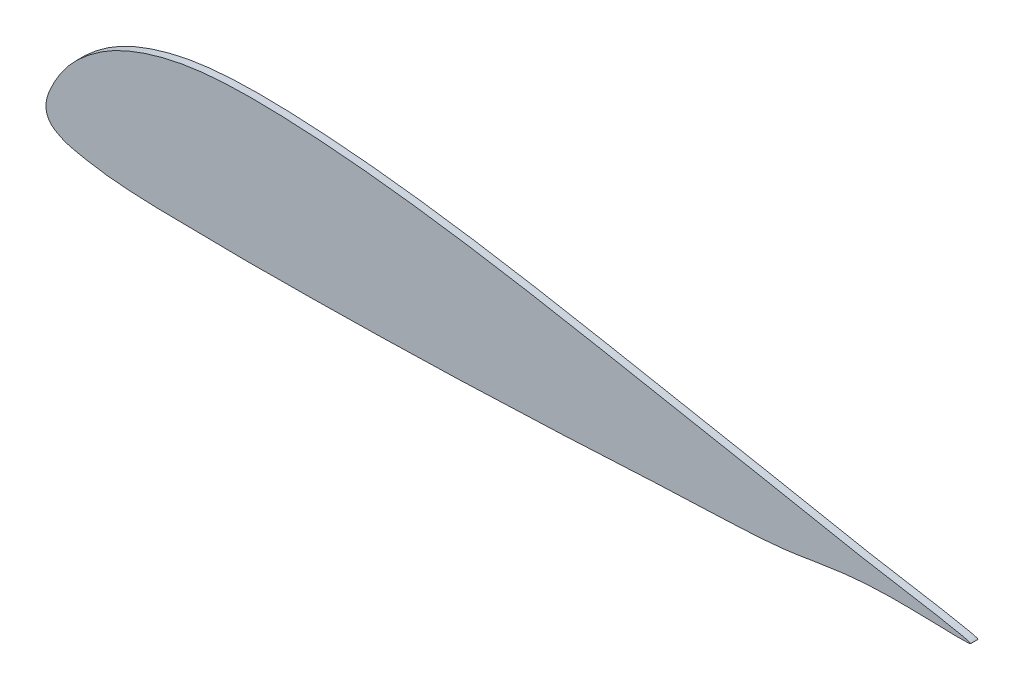
SolidWorks part; units mm, degrees
material "Cedar"
ref_plane "Front Plane" through (0, 0, 0) normal (0, 0, 1) x (1, 0, 0)
ref_plane "Top Plane" through (0, 0, 0) normal (0, 1, 0) x (1, 0, 0)
ref_plane "Right Plane" through (0, 0, 0) normal (1, 0, 0) x (0, 0, -1)
sketch "Sketch11" plane through (0, 0, 0) normal (0, 0, 1) x (1, 0, 0)
  line L0 (-43.8005, 0) -> (380.3083, 0) construction
  line L1 (0, 103.9604) -> (0, -61.3214) construction
  line L2 (71, 38.6091) -> (104.7082, 38.6091) construction
  line L3 (300.2276, 54.6091) -> (24.1354, 54.6091) construction
  line L4 (360.1442, 7.9921) -> (360.1442, 43.239) construction
  line L5 (104.7082, 38.6091) -> (88.9969, 38.6091) construction
  line L6 (250, 2.9185) -> (250, 63.6488) construction
  line L7 (150, 0.322) -> (150, 76.2348) construction
  line L8 (257, 52.6091) -> (310.8064, 52.6091)
  line L9 (26.8374, 56.6091) -> (71.2374, 56.6091)
  line L10 (53, 0.8986) -> (53, 69.6242)
  line L11 (57, 70.9042) -> (57, 0.7526)
  line L12 (71.2374, 56.6091) -> (142.6837, 56.6091)
  line L13 (147.6837, 61.6091) -> (147.6837, 76.3956)
  line L14 (151.6838, 76.1131) -> (151.6838, 61.6091)
  line L15 (156.6838, 56.6091) -> (243, 56.6091)
  line L16 (248, 61.6091) -> (248, 63.9838)
  line L17 (257, 56.6091) -> (289.5358, 56.6091)
  line L18 (248, 47.6091) -> (248, 2.8398)
  line L19 (252, 61.6091) -> (252, 63.3114)
  line L20 (362.1442, 42.8626) -> (362.1442, 8.0635)
  line L21 (358.1442, 7.9209) -> (358.1442, 43.6156)
  line L22 (151.6838, 0.3468) -> (151.6838, 47.6091)
  line L23 (156.6838, 52.6091) -> (243, 52.6091)
  line L24 (142.6837, 52.6091) -> (21.6293, 52.6091)
  line L25 (147.6837, 47.6091) -> (147.6837, 0.2878)
  line L26 (252, 47.6091) -> (252, 2.9976)
  line L27 (55, 70.2814) -> (55, 0.8215) construction
  line L28 (500.1442, 88.475) -> (500.1442, -17.1372) construction
  circle A0 centre (71, 38.6091) radius 14
  arc A1 (248, 47.6091) -> (243, 52.6091) centre (243, 47.6091) ccw
  arc A2 (147.6837, 47.6091) -> (142.6837, 52.6091) centre (142.6837, 47.6091) ccw
  arc A3 (151.6838, 47.6091) -> (156.6838, 52.6091) centre (156.6838, 47.6091) cw
  arc A4 (156.6838, 56.6091) -> (151.6838, 61.6091) centre (156.6838, 61.6091) cw
  arc A5 (147.6837, 61.6091) -> (142.6837, 56.6091) centre (142.6837, 61.6091) cw
  arc A6 (257, 52.6091) -> (252, 47.6091) centre (257, 47.6091) ccw
  arc A7 (257, 56.6091) -> (252, 61.6091) centre (257, 61.6091) cw
  arc A8 (243, 56.6091) -> (248, 61.6091) centre (243, 61.6091) ccw
  circle A9 centre (264.4, 40.2091) radius 12.4
  spline S0 degree 3 poles (5.2055, 33.3883) (8.3496, 38.4375) (12.1035, 43.4755) (16.9159, 48.515) (21.6177, 52.7069) (26.6422, 56.5456) (31.6627, 59.9068) (36.9892, 62.9567) (42.8619, 65.7826) (49.0168, 68.273) (55.4478, 70.4816) (61.4972, 72.2302) (68.0467, 73.8177) (74.3979, 75.051) (80.8825, 76.0083) (86.7438, 76.6697) (93.1859, 77.1993) (100.8735, 77.5954) (109.531, 77.773) (119.5404, 77.7056) (130.1167, 77.3864) (141.1364, 76.8376) (151.9182, 76.1212) (163.3231, 75.2) (175.9581, 73.987) (190.0575, 72.4145) (206.5823, 70.3225) (223.85, 67.8568) (240.4904, 65.2434) (253.8174, 63.0166) (268.6705, 60.4321) (285.232, 57.4255) (303.8938, 53.9257) (320.0111, 50.8601) (334.6114, 48.0737) (347.9319, 45.5391) (362.6553, 42.7654) (376.82, 40.1027) (391.3063, 37.3496) (404.1411, 34.8487) (419.3457, 31.8104) (436.364, 28.5258) (455.9997, 25.1096) (476.5677, 21.5774) (486.7341, 19.9981) (503.1995, 16.4828) (494.0454, 16.079) (487.8931, 16.3457) (477.383, 16.5668) (465.767, 16.8138) (452.7435, 16.8186) (439.1741, 16.1147) (425.2643, 14.4643) (412.0417, 12.2109) (396.9272, 9.9539) (381.3257, 8.8145) (365.9637, 8.1886) (351.799, 7.7061) (338.7226, 7.1495) (326.1387, 6.5056) (315.7861, 5.9505) (307.2533, 5.4916) (297.4115, 4.9796) (286.8565, 4.4714) (277.2883, 4.0439) (269.1855, 3.6963) (261.4554, 3.3751) (251.8585, 2.9904) (241.2598, 2.5754) (231.9793, 2.2273) (223.4506, 1.9259) (216.5377, 1.6954) (207.3161, 1.4113) (198.2656, 1.1695) (188.832, 0.9605) (181.1944, 0.8118) (173.3008, 0.675) (165.598, 0.5531) (157.1849, 0.4277) (148.2555, 0.2964) (137.6659, 0.1399) (127.333, 0.0247) (116.0359, -0.0123) (106.2761, 0.023) (96.7775, 0.1009) (88.6912, 0.1891) (80.0667, 0.3031) (71.5319, 0.4229) (61.8979, 0.5932) (53.0114, 0.8627) (44.0349, 1.3341) (36.2173, 1.9595) (28.3052, 2.9117) (21.1381, 4.1529) (14.9806, 5.476) (10.1274, 6.7093) (6.4953, 8.5231) (3.4169, 10.3581) (1.2362, 12.9218) (0.0423, 16.1496) (-0.1077, 19.6683) (0.8487, 24.1335) (2.8481, 28.6747) (5.2055, 33.3883) (8.3496, 38.4375) (12.1035, 43.4755) knots -0.015232 -0.009466 -0.004823 0 0.007707 0.013288 0.020114 0.025893 0.031552 0.037566 0.043618 0.050376 0.056746 0.063265 0.06857 0.076221 0.081956 0.087512 0.093268 0.100637 0.109759 0.118294 0.129567 0.14034 0.150184 0.160799 0.173412 0.186871 0.201804 0.221556 0.237286 0.250491 0.260611 0.280864 0.299143 0.315493 0.328286 0.342107 0.354686 0.371592 0.383765 0.397312 0.409372 0.428651 0.447018 0.468574 0.482905 0.490874 0.494014 0.502595 0.511845 0.523193 0.536597 0.549343 0.56248 0.577047 0.588116 0.606637 0.622219 0.632562 0.647602 0.66005 0.668982 0.677569 0.68475 0.697468 0.708114 0.712434 0.72091 0.730477 0.740196 0.751569 0.75732 0.764863 0.771562 0.783988 0.791033 0.798836 0.806068 0.813853 0.821103 0.830389 0.839665 0.851715 0.860257 0.872319 0.879926 0.887714 0.895694 0.904857 0.912386 0.923545 0.930552 0.938366 0.946209 0.953581 0.959372 0.964437 0.967975 0.971074 0.974748 0.97743 0.980891 0.984768 0.990534 0.995177 1 1.007707 1.013288 1.020114 only from (7.8664, 37.5601) to (7.8664, 37.5601)
  point P120 (251.7708, 7.1763)
  dimension "D3" = 28
  dimension "D11" = 5
  dimension "D12" = 5
  dimension "D13" = 24.8
  dimension "D1" = 4
  dimension "D2" = 2
  dimension "D4" = 2
  dimension "D5" = 4
  dimension "D6" = 2
  dimension "D7" = 4
  dimension "D8" = 2
  dimension "D9" = 4
  dimension "D10" = 2
  dimension "D14" = 55
  dimension "D15" = 150
  dimension "D16" = 250
  dimension "D17" = 140
extrude "Boss-Extrude33" add sketch "Sketch11" along normal blind 4 contours A0 S0 region at (71, 38.6091, 0)
extrude "Boss-Extrude34" add sketch "Sketch11<11>" along normal blind 4 contours S0
sketch "Sketch11<11>" plane through (0, 0, 0) normal (0, 0, 1) x (1, 0, 0) same geometry as "Sketch11"
sketch "Sketch12" plane through (0, 0, 4) normal (0, 0, 1) x (1, 0, 0)
  spline S1 degree 3 poles (12.1035, 43.4755) (8.3496, 38.4375) (5.2055, 33.3883) (2.8481, 28.6747) (0.8487, 24.1335) (-0.1077, 19.6683) (0.0423, 16.1496) (1.2362, 12.9218) (3.4169, 10.3581) (6.4953, 8.5231) (10.1274, 6.7093) (14.9806, 5.476) (21.1381, 4.1529) (28.3052, 2.9117) (36.2173, 1.9595) (44.0349, 1.3341) (53.0114, 0.8627) (61.8979, 0.5932) (71.5319, 0.4229) (80.0667, 0.3031) (88.6912, 0.1891) (96.7775, 0.1009) (106.2761, 0.023) (116.0359, -0.0123) (127.333, 0.0247) (137.6659, 0.1399) (148.2555, 0.2964) (157.1849, 0.4277) (165.598, 0.5531) (173.3008, 0.675) (181.1944, 0.8118) (188.832, 0.9605) (198.2656, 1.1695) (207.3161, 1.4113) (216.5377, 1.6954) (223.4506, 1.9259) (231.9793, 2.2273) (241.2598, 2.5754) (251.8585, 2.9904) (261.4554, 3.3751) (269.1855, 3.6963) (277.2883, 4.0439) (286.8565, 4.4714) (297.4115, 4.9796) (307.2533, 5.4916) (315.7861, 5.9505) (326.1387, 6.5056) (338.7226, 7.1495) (351.799, 7.7061) (365.9637, 8.1886) (381.3257, 8.8145) (396.9272, 9.9539) (412.0417, 12.2109) (425.2643, 14.4643) (439.1741, 16.1147) (452.7435, 16.8186) (465.767, 16.8138) (477.383, 16.5668) (487.8931, 16.3457) (494.0454, 16.079) (503.1995, 16.4828) (486.7341, 19.9981) (476.5677, 21.5774) (455.9997, 25.1096) (436.364, 28.5258) (419.3457, 31.8104) (404.1411, 34.8487) (391.3063, 37.3496) (376.82, 40.1027) (362.6553, 42.7654) (347.9319, 45.5391) (334.6114, 48.0737) (320.0111, 50.8601) (303.8938, 53.9257) (285.232, 57.4255) (268.6705, 60.4321) (253.8174, 63.0166) (240.4904, 65.2434) (223.85, 67.8568) (206.5823, 70.3225) (190.0575, 72.4145) (175.9581, 73.987) (163.3231, 75.2) (151.9182, 76.1212) (141.1364, 76.8376) (130.1167, 77.3864) (119.5404, 77.7056) (109.531, 77.773) (100.8735, 77.5954) (93.1859, 77.1993) (86.7438, 76.6697) (80.8825, 76.0083) (74.3979, 75.051) (68.0467, 73.8177) (61.4972, 72.2302) (55.4478, 70.4816) (49.0168, 68.273) (42.8619, 65.7826) (36.9892, 62.9567) (31.6627, 59.9068) (26.6422, 56.5456) (21.6177, 52.7069) (16.9159, 48.515) (12.1035, 43.4755) (8.3496, 38.4375) (5.2055, 33.3883) knots -0.020114 -0.013288 -0.007707 0 0.004823 0.009466 0.015232 0.019109 0.02257 0.025252 0.028926 0.032025 0.035563 0.040628 0.046419 0.053791 0.061634 0.069448 0.076455 0.087614 0.095143 0.104306 0.112286 0.120074 0.127681 0.139743 0.148285 0.160335 0.169611 0.178897 0.186147 0.193932 0.201164 0.208967 0.216012 0.228438 0.235137 0.24268 0.248431 0.259804 0.269523 0.27909 0.287566 0.291886 0.302532 0.31525 0.322431 0.331018 0.33995 0.352398 0.367438 0.377781 0.393363 0.411884 0.422953 0.43752 0.450657 0.463403 0.476807 0.488155 0.497405 0.505986 0.509126 0.517095 0.531426 0.552982 0.571349 0.590628 0.602688 0.616235 0.628408 0.645314 0.657893 0.671714 0.684507 0.700857 0.719136 0.739389 0.749509 0.762714 0.778444 0.798196 0.813129 0.826588 0.839201 0.849816 0.85966 0.870433 0.881706 0.890241 0.899363 0.906732 0.912488 0.918044 0.923779 0.93143 0.936735 0.943254 0.949624 0.956382 0.962434 0.968448 0.974107 0.979886 0.986712 0.992293 1 1.004823 1.009466 1.015232 only from (7.8664, 37.5601) to (7.8664, 37.5601) construction
  spline S2 degree 3 poles (487.5145, 12.3234) (489.0707, 12.2744) (490.4539, 12.2242) (493.2206, 12.173) (494.6041, 12.1722) (496.6795, 12.2138) (497.3713, 12.2322) (498.4092, 12.2794) (498.7548, 12.2987) (499.4444, 12.3521) (499.7885, 12.3859) (500.4729, 12.4889) (500.8153, 12.56) (501.3093, 12.7169) (501.4711, 12.7775) (501.788, 12.9172) (501.9439, 12.9968) (502.3916, 13.2604) (502.6657, 13.4693) (503.1626, 13.9575) (503.3766, 14.2286) (503.7327, 14.818) (503.8755, 15.1403) (504.023, 15.6347) (504.0617, 15.8024) (504.1179, 16.1434) (504.1354, 16.3179) (504.1539, 16.8368) (504.1228, 17.1794) (504.0103, 17.6883) (503.9618, 17.856) (503.8454, 18.1806) (503.7773, 18.3385) (503.5434, 18.7995) (503.3459, 19.0912) (503.0065, 19.4804) (502.8857, 19.6032) (502.6291, 19.8349) (502.4925, 19.9444) (502.0702, 20.2462) (501.7704, 20.4135) (501.1457, 20.7019) (500.8203, 20.824) (499.8388, 21.1541) (499.1741, 21.3316) (497.8401, 21.6677) (497.1699, 21.8229) (495.1556, 22.2725) (493.8071, 22.55) (489.7598, 23.3717) (487.0574, 23.8967) (481.6361, 24.8554) (478.9165, 25.2853) (470.7685, 26.6351) (465.3421, 27.5658) (454.4907, 29.4357) (449.0652, 30.3716) (440.9346, 31.818) (438.2259, 32.3082) (432.8123, 33.3105) (430.1073, 33.8216) (421.9963, 35.3769) (416.5947, 36.4456) (408.4932, 38.0544) (405.7927, 38.5904) (400.3899, 39.6525) (397.6879, 40.1796) (389.5798, 41.7491) (384.1715, 42.7782) (373.3528, 44.8243) (367.9424, 45.8416) (357.1221, 47.878) (351.7121, 48.8973) (340.8943, 50.949) (335.4863, 51.9799) (319.2625, 55.0738) (308.4469, 57.1385) (286.8039, 61.1975) (275.9763, 63.191) (254.2926, 67.0102) (243.4363, 68.8341) (221.6801, 72.2245) (210.7804, 73.7924) (188.9252, 76.598) (177.9696, 77.8355) (161.4807, 79.3641) (155.9808, 79.8183) (144.9811, 80.603) (139.48, 80.9326) (128.4752, 81.4404) (122.9715, 81.6225) (111.9601, 81.7775) (106.4524, 81.7473) (98.1864, 81.4602) (95.4303, 81.3247) (89.9163, 80.9534) (87.1567, 80.7173) (81.6422, 80.1235) (78.8985, 79.7668) (73.4419, 78.9157) (70.7292, 78.4205) (62.6409, 76.7146) (57.3144, 75.2854) (50.7484, 73.0894) (49.4388, 72.6291) (46.8338, 71.6669) (45.5427, 71.1667) (41.7068, 69.6026) (39.1994, 68.4758) (34.3045, 66.0195) (31.9186, 64.6875) (27.2732, 61.8099) (25.013, 60.2658) (20.6088, 56.981) (18.467, 55.2368) (15.3589, 52.444) (14.3454, 51.4885) (12.3762, 49.5363) (11.4197, 48.5374) (8.654, 45.4567) (6.9585, 43.2827) (4.5908, 39.8793) (3.8283, 38.7231) (2.3688, 36.3578) (1.6742, 35.1437) (0.376, 32.6776) (-0.2346, 31.426) (-1.1162, 29.5319) (-1.4025, 28.8969) (-1.9479, 27.6137) (-2.2075, 26.9641) (-2.9241, 25.0014) (-3.3205, 23.6732) (-3.7313, 21.6364) (-3.8375, 20.9501) (-3.9417, 19.9073) (-3.9673, 19.5564) (-3.9981, 18.8569) (-4.0033, 18.508) (-3.9872, 17.4641) (-3.934, 16.7719) (-3.782, 15.7397) (-3.7193, 15.3967) (-3.5677, 14.713) (-3.4785, 14.3712) (-2.9737, 12.6966) (-2.3807, 11.4461) (-1.3944, 9.9983) (-1.1845, 9.7141) (-0.748, 9.1669) (-0.5206, 8.9025) (0.1883, 8.1361) (0.6961, 7.6608) (1.5106, 7.0008) (1.7917, 6.7891) (2.3654, 6.3839) (2.6569, 6.191) (3.5423, 5.6349) (4.1471, 5.2939) (5.9773, 4.3044) (7.2254, 3.7023) (9.1767, 2.9629) (9.8395, 2.742) (11.1836, 2.3383) (11.8588, 2.1571) (13.2123, 1.8172) (13.8905, 1.6576) (15.2478, 1.3445) (15.9271, 1.1926) (17.9669, 0.7501) (19.3293, 0.4728) (23.4236, -0.3101) (26.1627, -0.7648) (31.6619, -1.5282) (34.4216, -1.8399) (39.9559, -2.358) (42.7306, -2.5641) (48.2909, -2.9007) (51.0763, -3.0315) (59.4274, -3.3528) (64.9947, -3.4667) (73.3456, -3.6019) (76.1292, -3.6419) (81.6965, -3.7186) (84.4801, -3.7559) (98.3982, -3.929) (109.5327, -4.0244) (126.2342, -3.9798) (131.8014, -3.9284) (142.9357, -3.7865) (148.5028, -3.7006) (165.2042, -3.4542) (176.3384, -3.2909) (193.0397, -2.9518) (198.6071, -2.8221) (209.7403, -2.5195) (215.3058, -2.3478) (232, -1.789) (243.1265, -1.3594) (265.3781, -0.4728) (276.5028, -0.0089) (293.1855, 0.7692) (298.7456, 1.0435) (309.8642, 1.6235) (315.4228, 1.9264) (326.5407, 2.5193) (332.0999, 2.8105) (343.2213, 3.3386) (348.7834, 3.5746) (359.9108, 3.9869) (365.4758, 4.1689) (373.8192, 4.5187) (376.5997, 4.6474) (382.1586, 4.9445) (384.9371, 5.1122) (390.4904, 5.5154) (393.2653, 5.7509) (397.4238, 6.1778) (398.8093, 6.3324) (401.5789, 6.6698) (402.9629, 6.8524) (407.1134, 7.4317) (409.8781, 7.8601) (415.4062, 8.7449) (418.1695, 9.2008) (423.6983, 10.0732) (426.4638, 10.4876) (431.9999, 11.2184) (434.7704, 11.5382) (443.0906, 12.3304) (448.6499, 12.6197) (459.787, 12.8465) (465.3644, 12.7928) (473.7339, 12.6451) (476.5244, 12.5847) (480.7099, 12.4958) (482.1051, 12.4655) (484.1982, 12.4152) (484.896, 12.3977) (485.9427, 12.3694) (486.466, 12.3548) (486.9895, 12.3393) (487.3384, 12.3288) (487.5145, 12.3234) (489.0707, 12.2744) (490.4539, 12.2242) knots -0.000488 -0.000488 0 0 0.003906 0.003906 0.007812 0.007812 0.009766 0.009766 0.010742 0.010742 0.011719 0.011719 0.012695 0.012695 0.013184 0.013184 0.013672 0.013672 0.014648 0.014648 0.015625 0.015625 0.016602 0.016602 0.01709 0.01709 0.017578 0.017578 0.018555 0.018555 0.019043 0.019043 0.019531 0.019531 0.020508 0.020508 0.020996 0.020996 0.021484 0.021484 0.022461 0.022461 0.023437 0.023437 0.025391 0.025391 0.027344 0.027344 0.03125 0.03125 0.039062 0.039062 0.046875 0.046875 0.0625 0.0625 0.078125 0.078125 0.085937 0.085937 0.09375 0.09375 0.109375 0.109375 0.117187 0.117187 0.125 0.125 0.140625 0.140625 0.15625 0.15625 0.171875 0.171875 0.1875 0.1875 0.21875 0.21875 0.25 0.25 0.28125 0.28125 0.3125 0.3125 0.34375 0.34375 0.359375 0.359375 0.375 0.375 0.390625 0.390625 0.40625 0.40625 0.414062 0.414062 0.421875 0.421875 0.429687 0.429687 0.4375 0.4375 0.453125 0.453125 0.457031 0.457031 0.460937 0.460937 0.46875 0.46875 0.476562 0.476562 0.484375 0.484375 0.492187 0.492187 0.496094 0.496094 0.5 0.5 0.507812 0.507812 0.511719 0.511719 0.515625 0.515625 0.519531 0.519531 0.521484 0.521484 0.523437 0.523437 0.527344 0.527344 0.529297 0.529297 0.530273 0.530273 0.53125 0.53125 0.533203 0.533203 0.53418 0.53418 0.535156 0.535156 0.539062 0.539062 0.540039 0.540039 0.541016 0.541016 0.542969 0.542969 0.543945 0.543945 0.544922 0.544922 0.546875 0.546875 0.550781 0.550781 0.552734 0.552734 0.554687 0.554687 0.556641 0.556641 0.558594 0.558594 0.5625 0.5625 0.570312 0.570312 0.578125 0.578125 0.585937 0.585937 0.59375 0.59375 0.609375 0.609375 0.617187 0.617187 0.625 0.625 0.65625 0.65625 0.671875 0.671875 0.6875 0.6875 0.71875 0.71875 0.734375 0.734375 0.75 0.75 0.78125 0.78125 0.8125 0.8125 0.828125 0.828125 0.84375 0.84375 0.859375 0.859375 0.875 0.875 0.890625 0.890625 0.898437 0.898437 0.90625 0.90625 0.914062 0.914062 0.917969 0.917969 0.921875 0.921875 0.929687 0.929687 0.9375 0.9375 0.945312 0.945312 0.953125 0.953125 0.96875 0.96875 0.984375 0.984375 0.992187 0.992187 0.996094 0.996094 0.998047 0.998047 0.999023 0.999512 0.999512 1 1 1.003906 1.003906 1.007812 only from (487.6874, 12.3179) to (487.6874, 12.3179)
  spline S3 degree 3 poles (487.5145, 12.3234) (489.0707, 12.2744) (490.4539, 12.2242) (493.2206, 12.173) (494.6041, 12.1722) (496.6795, 12.2138) (497.3713, 12.2322) (498.4092, 12.2794) (498.7548, 12.2987) (499.4444, 12.3521) (499.7885, 12.3859) (500.4729, 12.4889) (500.8153, 12.56) (501.3093, 12.7169) (501.4711, 12.7775) (501.788, 12.9172) (501.9439, 12.9968) (502.3916, 13.2604) (502.6657, 13.4693) (503.1626, 13.9575) (503.3766, 14.2286) (503.7327, 14.818) (503.8755, 15.1403) (504.023, 15.6347) (504.0617, 15.8024) (504.1179, 16.1434) (504.1354, 16.3179) (504.1539, 16.8368) (504.1228, 17.1794) (504.0103, 17.6883) (503.9618, 17.856) (503.8454, 18.1806) (503.7773, 18.3385) (503.5434, 18.7995) (503.3459, 19.0912) (503.0065, 19.4804) (502.8857, 19.6032) (502.6291, 19.8349) (502.4925, 19.9444) (502.0702, 20.2462) (501.7704, 20.4135) (501.1457, 20.7019) (500.8203, 20.824) (499.8388, 21.1541) (499.1741, 21.3316) (497.8401, 21.6677) (497.1699, 21.8229) (495.1556, 22.2725) (493.8071, 22.55) (489.7598, 23.3717) (487.0574, 23.8967) (481.6361, 24.8554) (478.9165, 25.2853) (470.7685, 26.6351) (465.3421, 27.5658) (454.4907, 29.4357) (449.0652, 30.3716) (440.9346, 31.818) (438.2259, 32.3082) (432.8123, 33.3105) (430.1073, 33.8216) (421.9963, 35.3769) (416.5947, 36.4456) (408.4932, 38.0544) (405.7927, 38.5904) (400.3899, 39.6525) (397.6879, 40.1796) (389.5798, 41.7491) (384.1715, 42.7782) (373.3528, 44.8243) (367.9424, 45.8416) (357.1221, 47.878) (351.7121, 48.8973) (340.8943, 50.949) (335.4863, 51.9799) (319.2625, 55.0738) (308.4469, 57.1385) (286.8039, 61.1975) (275.9763, 63.191) (254.2926, 67.0102) (243.4363, 68.8341) (221.6801, 72.2245) (210.7804, 73.7924) (188.9252, 76.598) (177.9696, 77.8355) (161.4807, 79.3641) (155.9808, 79.8183) (144.9811, 80.603) (139.48, 80.9326) (128.4752, 81.4404) (122.9715, 81.6225) (111.9601, 81.7775) (106.4524, 81.7473) (98.1864, 81.4602) (95.4303, 81.3247) (89.9163, 80.9534) (87.1567, 80.7173) (81.6422, 80.1235) (78.8985, 79.7668) (73.4419, 78.9157) (70.7292, 78.4205) (62.6409, 76.7146) (57.3144, 75.2854) (50.7484, 73.0894) (49.4388, 72.6291) (46.8338, 71.6669) (45.5427, 71.1667) (41.7068, 69.6026) (39.1994, 68.4758) (34.3045, 66.0195) (31.9186, 64.6875) (27.2732, 61.8099) (25.013, 60.2658) (20.6088, 56.981) (18.467, 55.2368) (15.3589, 52.444) (14.3454, 51.4885) (12.3762, 49.5363) (11.4197, 48.5374) (8.654, 45.4567) (6.9585, 43.2827) (4.5908, 39.8793) (3.8283, 38.7231) (2.3688, 36.3578) (1.6742, 35.1437) (0.376, 32.6776) (-0.2346, 31.426) (-1.1162, 29.5319) (-1.4025, 28.8969) (-1.9479, 27.6137) (-2.2075, 26.9641) (-2.9241, 25.0014) (-3.3205, 23.6732) (-3.7313, 21.6364) (-3.8375, 20.9501) (-3.9417, 19.9073) (-3.9673, 19.5564) (-3.9981, 18.8569) (-4.0033, 18.508) (-3.9872, 17.4641) (-3.934, 16.7719) (-3.782, 15.7397) (-3.7193, 15.3967) (-3.5677, 14.713) (-3.4785, 14.3712) (-2.9737, 12.6966) (-2.3807, 11.4461) (-1.3944, 9.9983) (-1.1845, 9.7141) (-0.748, 9.1669) (-0.5206, 8.9025) (0.1883, 8.1361) (0.6961, 7.6608) (1.5106, 7.0008) (1.7917, 6.7891) (2.3654, 6.3839) (2.6569, 6.191) (3.5423, 5.6349) (4.1471, 5.2939) (5.9773, 4.3044) (7.2254, 3.7023) (9.1767, 2.9629) (9.8395, 2.742) (11.1836, 2.3383) (11.8588, 2.1571) (13.2123, 1.8172) (13.8905, 1.6576) (15.2478, 1.3445) (15.9271, 1.1926) (17.9669, 0.7501) (19.3293, 0.4728) (23.4236, -0.3101) (26.1627, -0.7648) (31.6619, -1.5282) (34.4216, -1.8399) (39.9559, -2.358) (42.7306, -2.5641) (48.2909, -2.9007) (51.0763, -3.0315) (59.4274, -3.3528) (64.9947, -3.4667) (73.3456, -3.6019) (76.1292, -3.6419) (81.6965, -3.7186) (84.4801, -3.7559) (98.3982, -3.929) (109.5327, -4.0244) (126.2342, -3.9798) (131.8014, -3.9284) (142.9357, -3.7865) (148.5028, -3.7006) (165.2042, -3.4542) (176.3384, -3.2909) (193.0397, -2.9518) (198.6071, -2.8221) (209.7403, -2.5195) (215.3058, -2.3478) (232, -1.789) (243.1265, -1.3594) (265.3781, -0.4728) (276.5028, -0.0089) (293.1855, 0.7692) (298.7456, 1.0435) (309.8642, 1.6235) (315.4228, 1.9264) (326.5407, 2.5193) (332.0999, 2.8105) (343.2213, 3.3386) (348.7834, 3.5746) (359.9108, 3.9869) (365.4758, 4.1689) (373.8192, 4.5187) (376.5997, 4.6474) (382.1586, 4.9445) (384.9371, 5.1122) (390.4904, 5.5154) (393.2653, 5.7509) (397.4238, 6.1778) (398.8093, 6.3324) (401.5789, 6.6698) (402.9629, 6.8524) (407.1134, 7.4317) (409.8781, 7.8601) (415.4062, 8.7449) (418.1695, 9.2008) (423.6983, 10.0732) (426.4638, 10.4876) (431.9999, 11.2184) (434.7704, 11.5382) (443.0906, 12.3304) (448.6499, 12.6197) (459.787, 12.8465) (465.3644, 12.7928) (473.7339, 12.6451) (476.5244, 12.5847) (480.7099, 12.4958) (482.1051, 12.4655) (484.1982, 12.4152) (484.896, 12.3977) (485.9427, 12.3694) (486.466, 12.3548) (486.9895, 12.3393) (487.3384, 12.3288) (487.5145, 12.3234) (489.0707, 12.2744) (490.4539, 12.2242) knots -0.000488 -0.000488 0 0 0.003906 0.003906 0.007812 0.007812 0.009766 0.009766 0.010742 0.010742 0.011719 0.011719 0.012695 0.012695 0.013184 0.013184 0.013672 0.013672 0.014648 0.014648 0.015625 0.015625 0.016602 0.016602 0.01709 0.01709 0.017578 0.017578 0.018555 0.018555 0.019043 0.019043 0.019531 0.019531 0.020508 0.020508 0.020996 0.020996 0.021484 0.021484 0.022461 0.022461 0.023437 0.023437 0.025391 0.025391 0.027344 0.027344 0.03125 0.03125 0.039062 0.039062 0.046875 0.046875 0.0625 0.0625 0.078125 0.078125 0.085937 0.085937 0.09375 0.09375 0.109375 0.109375 0.117187 0.117187 0.125 0.125 0.140625 0.140625 0.15625 0.15625 0.171875 0.171875 0.1875 0.1875 0.21875 0.21875 0.25 0.25 0.28125 0.28125 0.3125 0.3125 0.34375 0.34375 0.359375 0.359375 0.375 0.375 0.390625 0.390625 0.40625 0.40625 0.414062 0.414062 0.421875 0.421875 0.429687 0.429687 0.4375 0.4375 0.453125 0.453125 0.457031 0.457031 0.460937 0.460937 0.46875 0.46875 0.476562 0.476562 0.484375 0.484375 0.492187 0.492187 0.496094 0.496094 0.5 0.5 0.507812 0.507812 0.511719 0.511719 0.515625 0.515625 0.519531 0.519531 0.521484 0.521484 0.523437 0.523437 0.527344 0.527344 0.529297 0.529297 0.530273 0.530273 0.53125 0.53125 0.533203 0.533203 0.53418 0.53418 0.535156 0.535156 0.539062 0.539062 0.540039 0.540039 0.541016 0.541016 0.542969 0.542969 0.543945 0.543945 0.544922 0.544922 0.546875 0.546875 0.550781 0.550781 0.552734 0.552734 0.554687 0.554687 0.556641 0.556641 0.558594 0.558594 0.5625 0.5625 0.570312 0.570312 0.578125 0.578125 0.585937 0.585937 0.59375 0.59375 0.609375 0.609375 0.617187 0.617187 0.625 0.625 0.65625 0.65625 0.671875 0.671875 0.6875 0.6875 0.71875 0.71875 0.734375 0.734375 0.75 0.75 0.78125 0.78125 0.8125 0.8125 0.828125 0.828125 0.84375 0.84375 0.859375 0.859375 0.875 0.875 0.890625 0.890625 0.898437 0.898437 0.90625 0.90625 0.914062 0.914062 0.917969 0.917969 0.921875 0.921875 0.929687 0.929687 0.9375 0.9375 0.945312 0.945312 0.953125 0.953125 0.96875 0.96875 0.984375 0.984375 0.992187 0.992187 0.996094 0.996094 0.998047 0.998047 0.999023 0.999512 0.999512 1 1 1.003906 1.003906 1.007812 only from (487.6874, 12.3179) to (487.6874, 12.3179)
  spline S4 degree 3 poles (12.1035, 43.4755) (8.3496, 38.4375) (5.2055, 33.3883) (2.8481, 28.6747) (0.8487, 24.1335) (-0.1077, 19.6683) (0.0423, 16.1496) (1.2362, 12.9218) (3.4169, 10.3581) (6.4953, 8.5231) (10.1274, 6.7093) (14.9806, 5.476) (21.1381, 4.1529) (28.3052, 2.9117) (36.2173, 1.9595) (44.0349, 1.3341) (53.0114, 0.8627) (61.8979, 0.5932) (71.5319, 0.4229) (80.0667, 0.3031) (88.6912, 0.1891) (96.7775, 0.1009) (106.2761, 0.023) (116.0359, -0.0123) (127.333, 0.0247) (137.6659, 0.1399) (148.2555, 0.2964) (157.1849, 0.4277) (165.598, 0.5531) (173.3008, 0.675) (181.1944, 0.8118) (188.832, 0.9605) (198.2656, 1.1695) (207.3161, 1.4113) (216.5377, 1.6954) (223.4506, 1.9259) (231.9793, 2.2273) (241.2598, 2.5754) (251.8585, 2.9904) (261.4554, 3.3751) (269.1855, 3.6963) (277.2883, 4.0439) (286.8565, 4.4714) (297.4115, 4.9796) (307.2533, 5.4916) (315.7861, 5.9505) (326.1387, 6.5056) (338.7226, 7.1495) (351.799, 7.7061) (365.9637, 8.1886) (381.3257, 8.8145) (396.9272, 9.9539) (412.0417, 12.2109) (425.2643, 14.4643) (439.1741, 16.1147) (452.7435, 16.8186) (465.767, 16.8138) (477.383, 16.5668) (487.8931, 16.3457) (494.0454, 16.079) (503.1995, 16.4828) (486.7341, 19.9981) (476.5677, 21.5774) (455.9997, 25.1096) (436.364, 28.5258) (419.3457, 31.8104) (404.1411, 34.8487) (391.3063, 37.3496) (376.82, 40.1027) (362.6553, 42.7654) (347.9319, 45.5391) (334.6114, 48.0737) (320.0111, 50.8601) (303.8938, 53.9257) (285.232, 57.4255) (268.6705, 60.4321) (253.8174, 63.0166) (240.4904, 65.2434) (223.85, 67.8568) (206.5823, 70.3225) (190.0575, 72.4145) (175.9581, 73.987) (163.3231, 75.2) (151.9182, 76.1212) (141.1364, 76.8376) (130.1167, 77.3864) (119.5404, 77.7056) (109.531, 77.773) (100.8735, 77.5954) (93.1859, 77.1993) (86.7438, 76.6697) (80.8825, 76.0083) (74.3979, 75.051) (68.0467, 73.8177) (61.4972, 72.2302) (55.4478, 70.4816) (49.0168, 68.273) (42.8619, 65.7826) (36.9892, 62.9567) (31.6627, 59.9068) (26.6422, 56.5456) (21.6177, 52.7069) (16.9159, 48.515) (12.1035, 43.4755) (8.3496, 38.4375) (5.2055, 33.3883) knots -0.020114 -0.013288 -0.007707 0 0.004823 0.009466 0.015232 0.019109 0.02257 0.025252 0.028926 0.032025 0.035563 0.040628 0.046419 0.053791 0.061634 0.069448 0.076455 0.087614 0.095143 0.104306 0.112286 0.120074 0.127681 0.139743 0.148285 0.160335 0.169611 0.178897 0.186147 0.193932 0.201164 0.208967 0.216012 0.228438 0.235137 0.24268 0.248431 0.259804 0.269523 0.27909 0.287566 0.291886 0.302532 0.31525 0.322431 0.331018 0.33995 0.352398 0.367438 0.377781 0.393363 0.411884 0.422953 0.43752 0.450657 0.463403 0.476807 0.488155 0.497405 0.505986 0.509126 0.517095 0.531426 0.552982 0.571349 0.590628 0.602688 0.616235 0.628408 0.645314 0.657893 0.671714 0.684507 0.700857 0.719136 0.739389 0.749509 0.762714 0.778444 0.798196 0.813129 0.826588 0.839201 0.849816 0.85966 0.870433 0.881706 0.890241 0.899363 0.906732 0.912488 0.918044 0.923779 0.93143 0.936735 0.943254 0.949624 0.956382 0.962434 0.968448 0.974107 0.979886 0.986712 0.992293 1 1.004823 1.009466 1.015232 only from (7.8664, 37.5601) to (7.8664, 37.5601)
  dimension "D1" = 4
